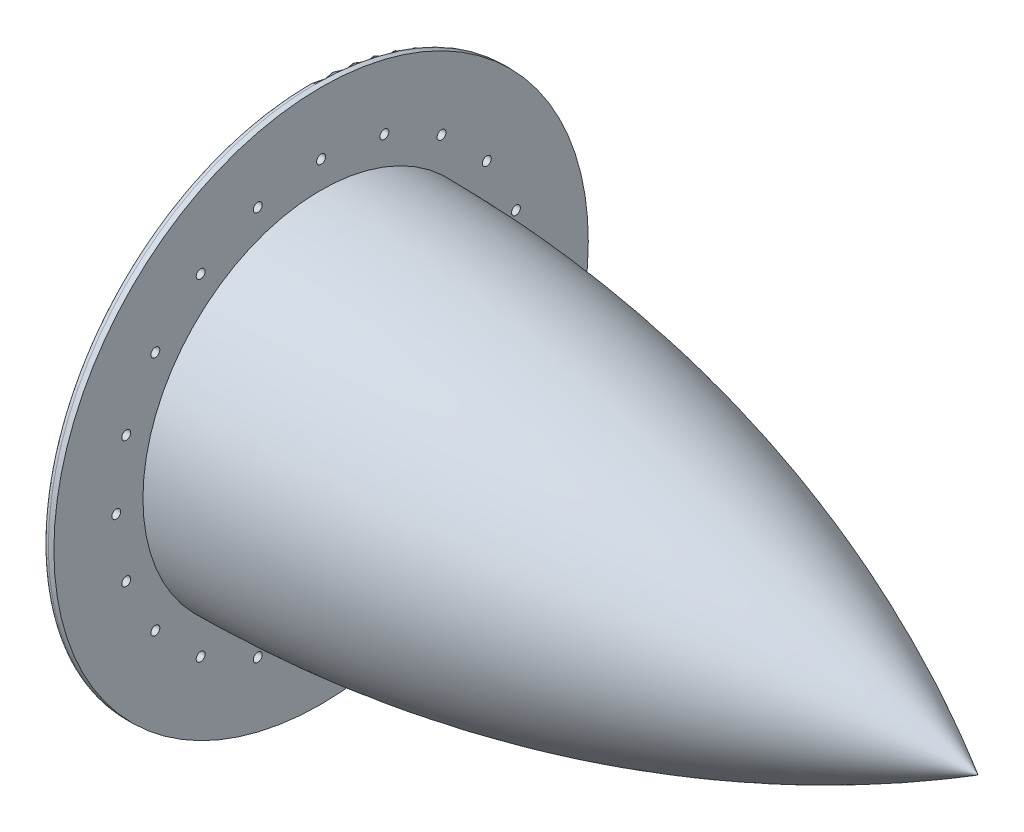
SolidWorks part; units mm, degrees
ref_plane "Front Plane" through (0, 0, 0) normal (0, 0, 1) x (1, 0, 0)
ref_plane "Top Plane" through (0, 0, 0) normal (0, 1, 0) x (1, 0, 0)
ref_plane "Right Plane" through (0, 0, 0) normal (1, 0, 0) x (0, 0, -1)
sketch "Sketch1" plane through (0, 0, 0) normal (0, 0, 1) x (1, 0, 0)
  line L0 (-149.6945, 0) -> (202.2403, 0) construction
  line L1 (-107.8411, 0) -> (-107.8411, 80)
  line L2 (-107.8411, 0) -> (192.1589, 0)
  arc A0 (-107.8411, 80) -> (192.1589, 0) centre (-105.5464, -513.8947) cw
  dimension "D1" = 300
  dimension "D2" = 80
revolve "Revolve1" add sketch "Sketch1" angle 360 about L0
shell "Shell1" thickness 10 removed face at (-107.8411, 0, 80)
sketch "Sketch2" plane through (-107.8411, 0, 0) normal (-1, 0, 0) x (0, 0, 1)
  circle A0 centre (0, 0) radius 120
  circle A1 centre (0, 0) radius 69.9999 construction
  circle A2 centre (0, 0) radius 69.9999
extrude "Boss-Extrude1" add sketch "Sketch2" against normal blind 5
sketch "Sketch3" plane through (-107.8411, 0, 0) normal (-1, 0, 0) x (0, 0, 1)
  circle A0 centre (0, 92) radius 2
  circle A1 centre (28.4296, 87.4972) radius 2
  circle A2 centre (54.0762, 74.4296) radius 2
  circle A3 centre (74.4296, 54.0762) radius 2
  circle A4 centre (87.4972, 28.4296) radius 2
  circle A5 centre (92, 0) radius 2
  circle A6 centre (87.4972, -28.4296) radius 2
  circle A7 centre (74.4296, -54.0762) radius 2
  circle A8 centre (54.0762, -74.4296) radius 2
  circle A9 centre (28.4296, -87.4972) radius 2
  circle A10 centre (0, -92) radius 2
  circle A11 centre (-28.4296, -87.4972) radius 2
  circle A12 centre (-54.0762, -74.4296) radius 2
  circle A13 centre (-74.4296, -54.0762) radius 2
  circle A14 centre (-87.4972, -28.4296) radius 2
  circle A15 centre (-92, 0) radius 2
  circle A16 centre (-87.4972, 28.4296) radius 2
  circle A17 centre (-74.4296, 54.0762) radius 2
  circle A18 centre (-54.0762, 74.4296) radius 2
  circle A19 centre (-28.4296, 87.4972) radius 2
  point P44 (0, 0)
  dimension "D1" = 92
  dimension "D2" = 20
extrude "Cut-Extrude1" cut sketch "Sketch3" against normal blind 5
fillet "Fillet1" radius 2.5 1 edges at (-107.8411, 0, 120)
